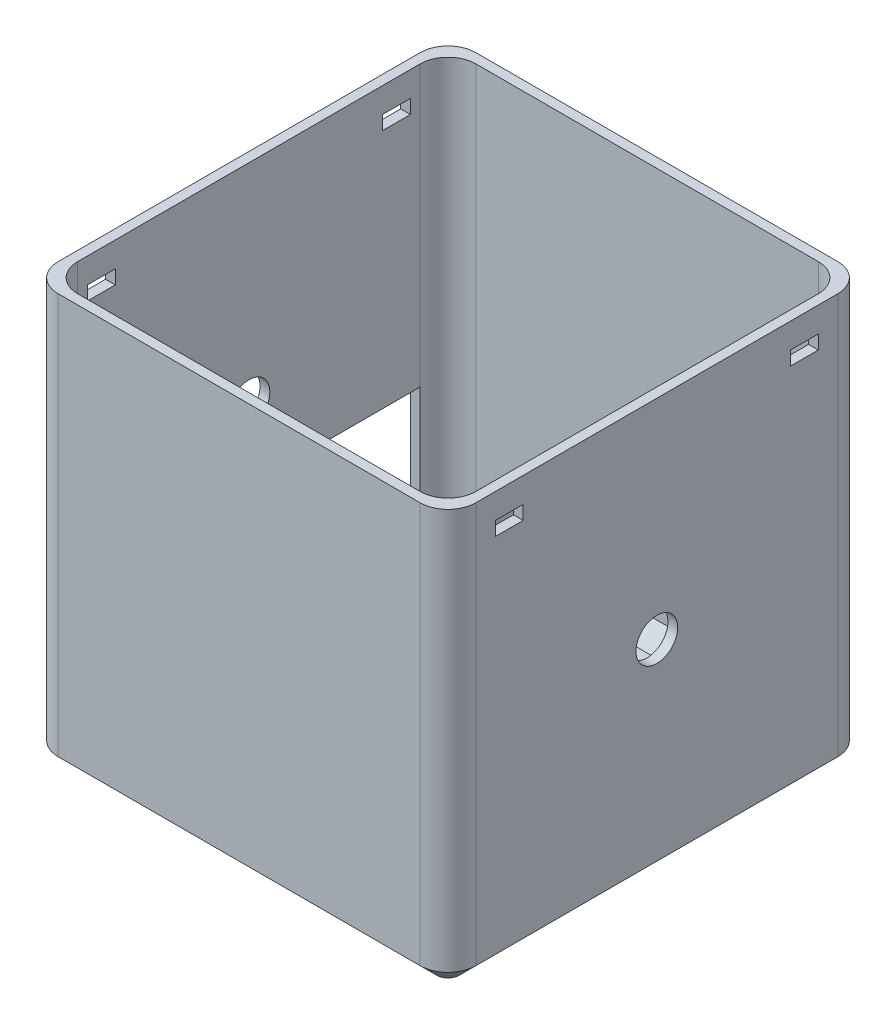
SolidWorks part; units mm, degrees
ref_plane "Front Plane" through (0, 0, 0) normal (0, 0, 1) x (1, 0, 0)
ref_plane "Top Plane" through (0, 0, 0) normal (0, 1, 0) x (1, 0, 0)
ref_plane "Right Plane" through (0, 0, 0) normal (1, 0, 0) x (0, 0, -1)
sketch "Sketch1" plane through (0, 0, 0) normal (0, 1, 0) x (1, 0, 0)
  line L1 (0, 0) -> (150, 0)
  line L2 (0, 0) -> (0, 150)
  line L3 (0, 150) -> (150, 150)
  line L4 (150, 0) -> (150, 150)
  dimension "D1" = 150
  dimension "D2" = 150
extrude "Boss-Extrude1" add sketch "Sketch1" along normal blind 150
shell "Shell1" thickness 3.5 removed face at (75, 150, -75)
fillet "Fillet2" radius 10 3 edges at (150, 75, -150) (150, 75, 0) (0, 75, 0)
fillet "Fillet3" radius 10 5 edges at (3.5, 76.75, -3.5) (146.5, 76.75, -3.5) (0, 75, -150) (146.5, 76.75, -146.5) (3.5, 76.75, -146.5)
sketch "Sketch2" plane through (150, 0, 0) normal (1, 0, 0) x (0, 0, -1)
  line L1 (150, 150) -> (150, 0) construction
  line L2 (10, 0) -> (140, 0) construction
  circle A0 centre (75, 75) radius 7.5
  dimension "D1" = 15
  dimension "D2" = 75
  dimension "D3" = 75
extrude "Cut-Extrude1" cut sketch "Sketch2" against normal blind 200
chamfer "Chamfer1" distance 6 angle 45 8 edges at (75, 0, 0) (0, 0, -75) (75, 0, -150) (2.9289, 0, -2.9289) (2.9289, 0, -147.0711) (147.0711, 0, -2.9289) (147.0711, 0, -147.0711) (150, 0, -75)
chamfer "Chamfer2" distance 6 angle 45 8 edges at (146.5, 3.5, -75) (75, 3.5, -146.5) (75, 3.5, -3.5) (143.5711, 3.5, -143.5711) (143.5711, 3.5, -6.4289) (6.4289, 3.5, -143.5711) (6.4289, 3.5, -6.4289) (3.5, 3.5, -75)
sketch "Sketch3" plane through (0, 0, 0) normal (-1, 0, 0) x (0, 0, 1)
  line L0 (-140, 150) -> (-10, 150) construction
  line L1 (-133, 141) -> (-123, 141)
  line L2 (-133, 141) -> (-133, 136)
  line L3 (-133, 136) -> (-123, 136)
  line L4 (-123, 141) -> (-123, 136)
  line L5 (-150, 6) -> (-150, 150) construction
  dimension "D1" = 10
  dimension "D2" = 5
  dimension "D3" = 9
  dimension "D4" = 17
extrude "Cut-Extrude2" cut sketch "Sketch3" against normal blind 234
sketch "Sketch4" plane through (0, 0, 0) normal (-1, 0, 0) x (0, 0, 1)
  line L0 (-140, 150) -> (-10, 150) construction
  line L1 (-17, 141) -> (-27, 141)
  line L2 (-17, 141) -> (-17, 136)
  line L3 (-17, 136) -> (-27, 136)
  line L4 (-27, 141) -> (-27, 136)
  line L5 (0, 150) -> (0, 6) construction
  dimension "D1" = 10
  dimension "D2" = 5
  dimension "D3" = 9
  dimension "D4" = 17
extrude "Cut-Extrude3" cut sketch "Sketch4" against normal blind 234
sketch "Sketch5" plane through (0, 3.5, 0) normal (0, 1, 0) x (1, 0, 0)
  line L0 (140.5, 13.5) -> (140.5, 136.5) construction
  line L1 (140.5, 100.5) -> (100.5, 100.5)
  line L2 (140.5, 100.5) -> (140.5, 140.5)
  line L3 (140.5, 140.5) -> (100.5, 140.5)
  line L4 (100.5, 100.5) -> (100.5, 140.5)
  line L5 (136.5, 140.5) -> (13.5, 140.5) construction
  dimension "D1" = 40
  dimension "D2" = 40
  dimension "D3" = 0
  dimension "D4" = 0
extrude "Cut-Extrude4" cut sketch "Sketch5" against normal blind 10
sketch "Sketch6" plane through (0, 3.5, 0) normal (0, 1, 0) x (1, 0, 0)
  line L0 (13.5, 146.5) -> (136.5, 146.5) construction
  line L1 (44.5, 101.5) -> (48.5, 101.5)
  line L2 (44.5, 101.5) -> (44.5, 146.5)
  line L3 (44.5, 146.5) -> (48.5, 146.5)
  line L4 (48.5, 101.5) -> (48.5, 146.5)
  line L6 (9.5, 136.5) -> (9.5, 13.5) construction
  dimension "D1" = 45
  dimension "D2" = 4
  dimension "D3" = 35
extrude "Boss-Extrude2" add sketch "Sketch6" along normal blind 40
fillet "Fillet4" radius 10 2 edges at (48.5, 26.5, -146.5) (48.5, 3.5, -121)
sketch "Sketch7" plane through (3.5, 0, 0) normal (1, 0, 0) x (0, 0, -1)
  line L1 (136.5, 9.5) -> (96.5, 9.5)
  line L2 (136.5, 9.5) -> (136.5, 49.5)
  line L3 (136.5, 49.5) -> (96.5, 49.5)
  line L4 (96.5, 9.5) -> (96.5, 49.5)
  dimension "D1" = 40
  dimension "D2" = 40
extrude "Cut-Extrude5" cut sketch "Sketch7" against normal blind 40
